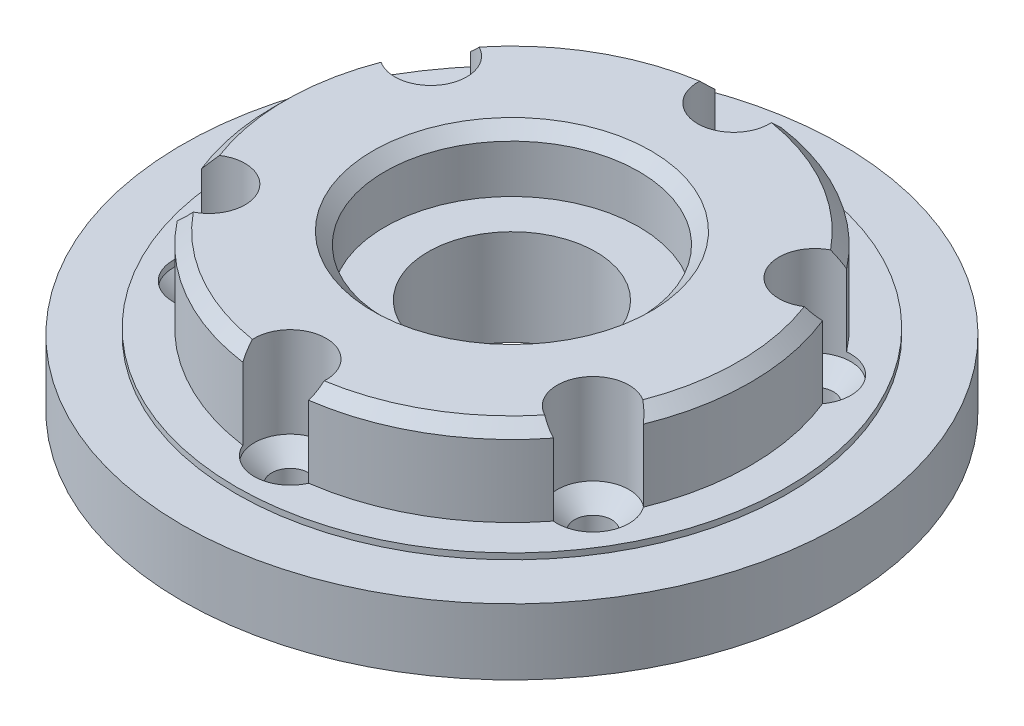
SolidWorks part; units mm, degrees
ref_plane "Ebene vorne" through (0, 0, 0) normal (0, 0, 1) x (1, 0, 0)
ref_plane "Ebene oben" through (0, 0, 0) normal (0, 1, 0) x (1, 0, 0)
ref_plane "Ebene rechts" through (0, 0, 0) normal (1, 0, 0) x (0, 0, -1)
sketch "Skizze1" plane through (0, 0, 0) normal (0, 0, 1) x (1, 0, 0)
  line L0 (0, 0) -> (0, -31946.5039) construction
  line L1 (7, 0) -> (27.5, 0)
  line L2 (27.5, 0) -> (27.5, 5.5)
  line L3 (27.5, 5.5) -> (23, 5.5)
  line L4 (19.9, 6) -> (19.9, 13)
  line L5 (19.9, 13) -> (10.6, 13)
  line L6 (10.6, 13) -> (10.6, 8)
  line L7 (10.6, 8) -> (7, 8)
  line L8 (7, 8) -> (7, 0)
  line L9 (19.9, 6) -> (23, 6)
  line L10 (23, 6) -> (23, 5.5)
  line L11 (0, 0) -> (-50000, 0) construction
  dimension "D1" = 39.8
  dimension "D2" = 46
  dimension "D3" = 7
  dimension "D4" = 0.5
  dimension "D5" = 13
  dimension "D6" = 55
  dimension "D7" = 21.2
  dimension "D8" = 14
  dimension "D9" = 5
revolve "Rotation1" add sketch "Skizze1" angle 360 about L0
chamfer "Fase1" distance 1 angle 45 2 edges at (0, 13, 19.9) (0, 13, 10.6)
hole_wizard "Ø3.1 (3.1) Durchmesser Bohrung1" positions "Skizze3" profile "Skizze4" hole size "Ø3.1" standard "DIN"
sketch "Skizze3" plane through (0, 0, 0) normal (0, -1, 0) x (-1, 0, 0)
  line L0 (0, -0.7104) -> (0, -50000.7104) construction
  circle A0 centre (0, 0) radius 18.5 construction
  point P11 (0, 18.5)
  point P18 (16.0215, 9.25)
  point P19 (16.0215, -9.25)
  point P20 (0, -18.5)
  point P21 (-16.0215, -9.25)
  point P22 (-16.0215, 9.25)
  dimension "D1" = 37
sketch "Skizze4" plane through (16.0215, 0, -9.25) normal (1, 0, 0) x (0, 0, -1)
  line L0 (0, 0) -> (0, 15.9313)
  line L1 (0, 15.9313) -> (1.55, 15)
  line L2 (1.55, 15) -> (1.55, 0.025)
  line L3 (1.55, 0.025) -> (1.575, 0)
  line L5 (1.575, 0) -> (0, 0)
  line L6 (-1.55, 0.025) -> (-1.575, 0) construction
  line L10 (0, 15.9313) -> (-1.55, 15) construction
  line L11 (0, -6.35) -> (0, 107.95) construction
  dimension "Bohrerdurchmesser" = 3.1
  dimension "Bohrungstiefe" = 15
  dimension "Senkdurchmesser2 (Oben)" = 3.15
  dimension "Senkwinkel2 (Oben)" = 90
  dimension "Spitzenwinkel" = 118
sketch "Skizze5" plane through (0, 13, 0) normal (0, 1, 0) x (1, 0, 0)
  line L0 (0, 0) -> (0, -50000) construction
  circle A0 centre (0, 18.5) radius 3
  circle A1 centre (16.0215, 9.25) radius 3
  circle A2 centre (16.0215, -9.25) radius 3
  circle A3 centre (0, -18.5) radius 3
  circle A4 centre (-16.0215, -9.25) radius 3
  circle A5 centre (-16.0215, 9.25) radius 3
  circle A6 centre (0, 0) radius 18.5 construction
  point P8 (-16.0215, 9.25)
  point P19 (0, 0)
  dimension "D1" = 6
  dimension "D2" = 37
  dimension "D3" = 6
extrude "Schnitt-Linear austragen1" cut sketch "Skizze5" against normal up to surface (7.5 mm away) up to face at (0, 5.5, 23)
chamfer "Fase2" distance 1.5 angle 45 6 edges at (0, 5.5, -20.05) (16.0215, 5.5, -10.8) (16.0215, 5.5, 7.7) (0, 5.5, 16.95) (-16.0215, 5.5, -10.8) (-16.0215, 5.5, 7.7)
